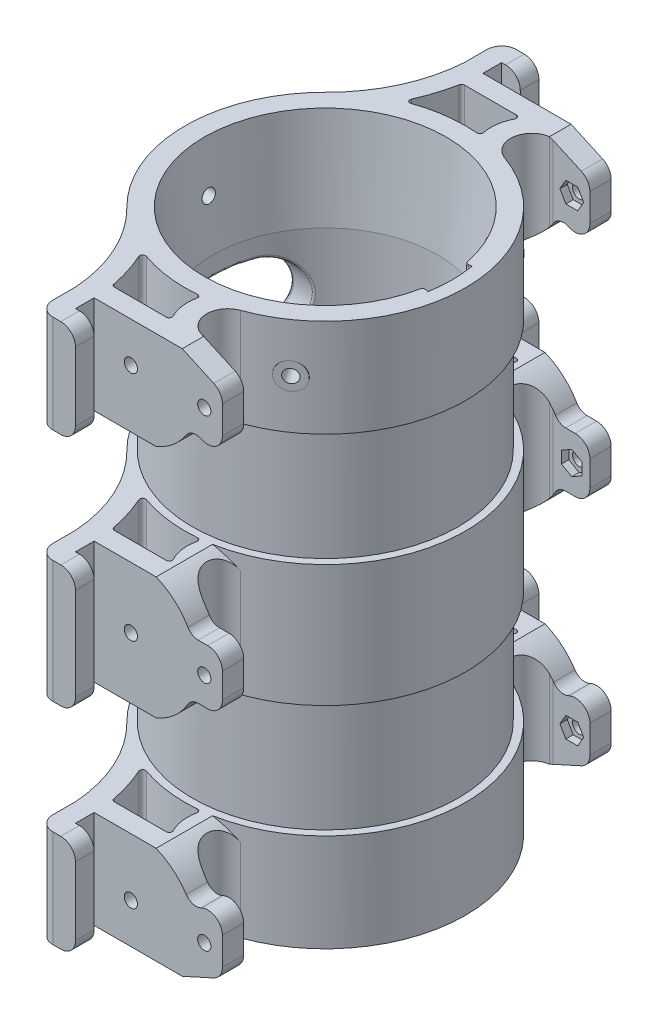
SolidWorks part; units mm, degrees
ref_plane "Front Plane" through (0, 0, 0) normal (0, 0, 1) x (1, 0, 0)
ref_plane "Top Plane" through (0, 0, 0) normal (0, 1, 0) x (1, 0, 0)
ref_plane "Right Plane" through (0, 0, 0) normal (1, 0, 0) x (0, 0, -1)
sketch "Sketch1" plane through (0, 0, 0) normal (0, 1, 0) x (1, 0, 0)
  line L0 (0, 38.25) -> (0, 45.25) construction
  circle A0 centre (0, 0) radius 38.25
  circle A1 centre (0, 0) radius 45.25
  dimension "D1" = 76.5
  dimension "D2" = 7
extrude "Boss-Extrude1" add sketch "Sketch1" along normal mid plane 185
sketch "Sketch2" plane through (0, -92.5, 0) normal (0, -1, 0) x (1, 0, 0)
  line L0 (0, 36.25) -> (0, 38.25) construction
  circle A0 centre (0, 0) radius 36.25
  circle A1 centre (0, 0) radius 38.25 construction
  circle A2 centre (0, 0) radius 38.25
  dimension "D1" = 2
extrude "Boss-Extrude2" add sketch "Sketch2" against normal blind 100 from offset 6.35 offset against normal yes
sketch "Sketch7" plane through (0, 0, 0) normal (1, 0, 0) x (0, 0, -1)
  line L0 (45.25, 92.5) -> (-45.25, 92.5) construction
  line L1 (12.5, 40) -> (-12.5, 40) construction
  line L2 (12.5, 27.5) -> (-12.5, 27.5)
  line L3 (12.5, 52.5) -> (-12.5, 52.5)
  circle A0 centre (0, 40) radius 12.5 construction
  arc A1 (12.5, 27.5) -> (12.5, 52.5) centre (12.5, 40) ccw
  arc A2 (-12.5, 52.5) -> (-12.5, 27.5) centre (-12.5, 40) ccw
  point P7 (0, 40)
  dimension "D2" = 25
  dimension "D3" = 25
  dimension "D1" = 52.5
extrude "Cut-Extrude4" cut sketch "Sketch7" against normal through all
sketch "Sketch8" plane through (0, 0, 0) normal (0, 1, 0) x (1, 0, 0)
  line L1 (17.5, -66.175) -> (128.1882, -66.175) construction
  line L2 (-18.85, -66.175) -> (-18.85, -78.875)
  line L3 (-18.85, -78.875) -> (-6.15, -78.875)
  line L4 (45.25, 0) -> (-45.25, 0) construction
  line L5 (31.75, 0) -> (50, 0) construction
  line L6 (-6.15, -78.875) -> (-6.15, -72.525)
  line L7 (-12.5, -72.525) -> (17.5, -72.525) construction
  line L8 (-6.15, -72.525) -> (-12.5, -72.525)
  line L9 (-12.5, -72.525) -> (-12.5, -66.175)
  line L10 (-12.5, -66.175) -> (43.65, -66.175)
  line L11 (-12.5, 66.175) -> (43.65, 66.175)
  line L12 (-12.5, 72.525) -> (-12.5, 66.175)
  line L13 (-6.15, 72.525) -> (-12.5, 72.525)
  line L14 (-6.15, 78.875) -> (-6.15, 72.525)
  line L15 (-18.85, 78.875) -> (-6.15, 78.875)
  line L16 (-18.85, 66.175) -> (-18.85, 78.875)
  line L18 (43.65, -66.175) -> (43.65, -58.9107)
  line L19 (43.65, -58.9107) -> (18.65, -58.9107)
  line L20 (43.65, 58.9107) -> (18.65, 58.9107)
  line L21 (43.65, 66.175) -> (43.65, 58.9107)
  line L22 (-12.5, -72.525) -> (-18.85, -72.525) construction
  arc A0 (-32.8241, -31.1471) -> (-18.85, -66.175) centre (-69.7381, -66.175) cw
  circle A1 centre (0, 0) radius 45.25 construction
  arc A2 (-32.8241, -31.1471) -> (15.7007, -42.4388) centre (0, 0) ccw
  arc A3 (-32.8241, 31.1471) -> (15.7007, 42.4388) centre (0, 0) cw
  arc A4 (-32.8241, 31.1471) -> (-18.85, 66.175) centre (-69.7381, 66.175) ccw
  arc A9 (18.65, -58.9107) -> (15.7007, -42.4388) centre (18.65, -50.4107) cw
  arc A10 (18.65, 58.9107) -> (15.7007, 42.4388) centre (18.65, 50.4107) ccw
  dimension "D1" = 8.5
  dimension "D2" = 62.5
  dimension "D3" = 25
extrude "Boss-Extrude3" add sketch "Sketch8" along normal up to surface and the other way up to surface up to face at (0, 92.5, 45.25) other way up to face at (0, -92.5, 45.25)
sketch "Sketch10" plane through (0, 0, 66.175) normal (0, 0, 1) x (1, 0, 0)
  line L0 (17.5, -92.5) -> (43.65, -92.5)
  line L1 (43.65, -92.5) -> (43.65, -80.6536)
  line L2 (-6.15, -59.2129) -> (-32.8241, -59.2129)
  line L3 (128.1882, -42.3564) -> (17.5, -92.5) construction
  line L4 (43.65, -80.6536) -> (17.5, -92.5)
  line L5 (43.65, 80.6536) -> (43.65, 92.5)
  line L6 (17.5, 92.5) -> (128.1882, 42.3564) construction
  line L7 (43.65, 92.5) -> (17.5, 92.5)
  line L8 (-12.5, 92.5) -> (43.65, 92.5) construction
  line L9 (17.5, 92.5) -> (43.65, 80.6536)
  line L10 (43.65, -60.1882) -> (43.65, -9.3209)
  line L11 (79.953, -43.7423) -> (23.8431, -69.161) construction
  line L12 (22.9086, -9.3209) -> (60.2886, -9.3209) construction
  line L21 (22.9086, -9.3209) -> (43.65, -9.3209)
  line L23 (43.65, -60.1882) -> (23.8431, -69.161)
  line L25 (-6.15, 92.5) -> (-6.15, -92.5) construction
  line L26 (-32.8241, 92.5) -> (-32.8241, -92.5) construction
  line L32 (-32.8241, -59.2129) -> (-32.8241, -20.7871)
  line L36 (-32.8241, -20.7871) -> (-6.15, -20.7871)
  line L40 (0, 0) -> (-32.8241, 0) construction
  line L45 (8.611, -59.2129) -> (-6.15, -59.2129)
  line L46 (8.611, -20.7871) -> (-6.15, -20.7871)
  line L47 (-32.8241, 59.2129) -> (-32.8241, 20.7871)
  line L48 (-6.15, 59.2129) -> (-32.8241, 59.2129)
  line L49 (8.611, 59.2129) -> (-6.15, 59.2129)
  line L50 (43.65, 60.1882) -> (23.8431, 69.161)
  line L51 (43.65, 60.1882) -> (43.65, 9.3209)
  line L52 (22.9086, 9.3209) -> (43.65, 9.3209)
  line L53 (8.611, 20.7871) -> (-6.15, 20.7871)
  line L54 (-32.8241, 20.7871) -> (-6.15, 20.7871)
  line L55 (43.65, 92.5) -> (43.65, -92.5) construction
  arc A6 (18.8427, -67.7035) -> (23.8431, -69.161) centre (22.1925, -65.5175) ccw construction
  arc A7 (18.8427, -67.7035) -> (8.611, -59.2129) centre (0, -80) ccw construction
  arc A10 (8.611, -20.7871) -> (19.4507, -11.3102) centre (0, 0) ccw construction
  arc A11 (22.9086, -9.3209) -> (19.4507, -11.3102) centre (22.9086, -13.3209) ccw construction
  arc A18 (18.8427, -67.7035) -> (23.8431, -69.161) centre (22.1925, -65.5175) ccw
  arc A19 (18.8427, -67.7035) -> (8.611, -59.2129) centre (0, -80) ccw
  arc A22 (8.611, -20.7871) -> (19.4507, -11.3102) centre (0, 0) ccw
  arc A23 (22.9086, -9.3209) -> (19.4507, -11.3102) centre (22.9086, -13.3209) ccw
  arc A24 (18.8427, 67.7035) -> (8.611, 59.2129) centre (0, 80) cw
  arc A25 (18.8427, 67.7035) -> (23.8431, 69.161) centre (22.1925, 65.5175) cw
  arc A26 (22.9086, 9.3209) -> (19.4507, 11.3102) centre (22.9086, 13.3209) cw
  arc A27 (8.611, 20.7871) -> (19.4507, 11.3102) centre (0, 0) cw
extrude "Cut-Extrude6" cut sketch "Sketch10" against normal up to surface and the other way through all up to face at (-41.5057, 40, 0)
sketch "Sketch11" plane through (0, 0, -78.875) normal (0, 0, -1) x (-1, 0, 0)
  line L3 (-43.65, 92.5) -> (-43.65, 80.6536)
  line L4 (-17.5, 92.5) -> (-43.65, 92.5)
  line L5 (-43.65, 80.6536) -> (-17.5, 92.5)
  line L6 (-43.65, 92.5) -> (-43.65, 80.6536)
  line L7 (-17.5, 92.5) -> (-43.65, 92.5)
  line L8 (-43.65, 80.6536) -> (-17.5, 92.5)
  line L9 (-43.65, -92.5) -> (-17.5, -92.5)
  line L10 (-43.65, -80.6536) -> (-43.65, -92.5)
  line L11 (-17.5, -92.5) -> (-43.65, -80.6536)
  line L12 (-43.65, -92.5) -> (-17.5, -92.5)
  line L13 (-43.65, -80.6536) -> (-43.65, -92.5)
  line L14 (-17.5, -92.5) -> (-43.65, -80.6536)
  line L20 (32.8241, 20.7871) -> (32.8241, 59.2129)
  line L21 (6.15, 20.7871) -> (32.8241, 20.7871)
  line L22 (-8.611, 20.7871) -> (6.15, 20.7871)
  line L23 (-43.65, 9.3209) -> (-22.9086, 9.3209)
  line L24 (-43.65, 60.1882) -> (-43.65, 9.3209)
  line L25 (-23.8431, 69.161) -> (-43.65, 60.1882)
  line L26 (6.15, 59.2129) -> (-8.611, 59.2129)
  line L27 (32.8241, 59.2129) -> (6.15, 59.2129)
  line L28 (32.8241, 20.7871) -> (32.8241, 59.2129)
  line L29 (6.15, 20.7871) -> (32.8241, 20.7871)
  line L30 (-8.611, 20.7871) -> (6.15, 20.7871)
  line L31 (-43.65, 9.3209) -> (-22.9086, 9.3209)
  line L32 (-43.65, 60.1882) -> (-43.65, 9.3209)
  line L33 (-23.8431, 69.161) -> (-43.65, 60.1882)
  line L34 (6.15, 59.2129) -> (-8.611, 59.2129)
  line L35 (32.8241, 59.2129) -> (6.15, 59.2129)
  line L36 (-22.9086, -9.3209) -> (-43.65, -9.3209)
  line L37 (-43.65, -9.3209) -> (-43.65, -60.1882)
  line L38 (-43.65, -60.1882) -> (-23.8431, -69.161)
  line L39 (-8.611, -59.2129) -> (6.15, -59.2129)
  line L40 (6.15, -59.2129) -> (32.8241, -59.2129)
  line L41 (32.8241, -59.2129) -> (32.8241, -20.7871)
  line L42 (32.8241, -20.7871) -> (6.15, -20.7871)
  line L43 (6.15, -20.7871) -> (-8.611, -20.7871)
  line L44 (-22.9086, -9.3209) -> (-43.65, -9.3209)
  line L45 (-43.65, -9.3209) -> (-43.65, -60.1882)
  line L46 (-43.65, -60.1882) -> (-23.8431, -69.161)
  line L47 (-8.611, -59.2129) -> (6.15, -59.2129)
  line L48 (6.15, -59.2129) -> (32.8241, -59.2129)
  line L49 (32.8241, -59.2129) -> (32.8241, -20.7871)
  line L50 (32.8241, -20.7871) -> (6.15, -20.7871)
  line L51 (6.15, -20.7871) -> (-8.611, -20.7871)
  arc A4 (-8.611, 20.7871) -> (-19.4507, 11.3102) centre (0, 0) ccw
  arc A5 (-22.9086, 9.3209) -> (-19.4507, 11.3102) centre (-22.9086, 13.3209) ccw
  arc A6 (-18.8427, 67.7035) -> (-23.8431, 69.161) centre (-22.1925, 65.5175) ccw
  arc A7 (-18.8427, 67.7035) -> (-8.611, 59.2129) centre (0, 80) ccw
  arc A8 (-8.611, 20.7871) -> (-19.4507, 11.3102) centre (0, 0) ccw
  arc A9 (-22.9086, 9.3209) -> (-19.4507, 11.3102) centre (-22.9086, 13.3209) ccw
  arc A10 (-18.8427, 67.7035) -> (-23.8431, 69.161) centre (-22.1925, 65.5175) ccw
  arc A11 (-18.8427, 67.7035) -> (-8.611, 59.2129) centre (0, 80) ccw
  arc A12 (-23.8431, -69.161) -> (-18.8427, -67.7035) centre (-22.1925, -65.5175) ccw
  arc A13 (-8.611, -59.2129) -> (-18.8427, -67.7035) centre (0, -80) ccw
  arc A14 (-19.4507, -11.3102) -> (-8.611, -20.7871) centre (0, 0) ccw
  arc A15 (-19.4507, -11.3102) -> (-22.9086, -9.3209) centre (-22.9086, -13.3209) ccw
  arc A16 (-23.8431, -69.161) -> (-18.8427, -67.7035) centre (-22.1925, -65.5175) ccw
  arc A17 (-8.611, -59.2129) -> (-18.8427, -67.7035) centre (0, -80) ccw
  arc A18 (-19.4507, -11.3102) -> (-8.611, -20.7871) centre (0, 0) ccw
  arc A19 (-19.4507, -11.3102) -> (-22.9086, -9.3209) centre (-22.9086, -13.3209) ccw
  dimension "D1" = 0
  dimension "D2" = 0
  dimension "D3" = 0
  dimension "D4" = 0
extrude "Cut-Extrude7" cut sketch "Sketch11" against normal up to surface (66.9486 mm away) up to face at (-3.9052, 0.3336, 17.6166)
fillet "Fillet5" radius 5 6 edges at (-18.85, -75.8565, -78.875) (-18.85, 0, -78.875) (-18.85, 75.8565, -78.875) (-18.85, 0, 78.875) (-18.85, -75.8565, 78.875) (-18.85, 75.8565, 78.875)
sketch "Sketch14" plane through (0, 0, -66.175) normal (0, 0, -1) x (-1, 0, 0)
  line L0 (0, 0) -> (-25, 0) construction
  line L5 (-25, 78.8696) -> (-25, 0) construction
  circle A3 centre (-25, 78.8696) radius 2.25
  circle A5 centre (-25, 0) radius 2.25
  circle A7 centre (-25, -78.8696) radius 2.25
  circle A8 centre (0, 0) radius 2.25
  circle A9 centre (0, 78.8696) radius 2.25
  circle A10 centre (0, -78.8696) radius 2.25
  dimension "D1" = 25
  dimension "D2" = 78.8696
  dimension "D3" = 4.5
extrude "Cut-Extrude8" cut sketch "Sketch14" against normal up to surface (7.2643 mm away) up to face at (27.8361, -73.0039, -58.9107)
sketch "Sketch15" plane through (0, 0, 66.175) normal (0, 0, 1) x (1, 0, 0)
  circle A1 centre (0, -78.8696) radius 2.25
  circle A3 centre (0, -78.8696) radius 2.25
  circle A5 centre (0, 78.8696) radius 2.25
  circle A7 centre (0, 78.8696) radius 2.25
  circle A9 centre (0, 0) radius 2.25
  circle A11 centre (0, 0) radius 2.25
  circle A13 centre (25, 78.8696) radius 2.25
  circle A14 centre (25, 78.8696) radius 2.25
  circle A15 centre (25, -78.8696) radius 2.25
  circle A16 centre (25, -78.8696) radius 2.25
  circle A17 centre (25, 0) radius 2.25
  circle A18 centre (25, 0) radius 2.25
  dimension "D1" = 0
  dimension "D2" = 0
  dimension "D3" = 0
  dimension "D4" = 0
  dimension "D5" = 0
  dimension "D6" = 0
extrude "Cut-Extrude9" cut sketch "Sketch15" against normal up to surface (7.2643 mm away) up to face at (27.8361, -73.0039, 58.9107)
sketch "Sketch16" plane through (0, 92.5, 0) normal (0, 1, 0) x (1, 0, 0)
  line L0 (-45.25, 0) -> (-47.75, 0) construction
  circle A0 centre (0, 0) radius 47.75
  circle A1 centre (0, 0) radius 45.25
  arc A2 (-32.8241, 31.1471) -> (-32.8241, -31.1471) centre (0, 0) ccw construction
  dimension "D1" = 2.5
extrude "Boss-Extrude4" add sketch "Sketch16" against normal up to surface (33.2871 mm away) up to face at (-10.3824, 59.2129, 65.577)
sketch "Sketch17" plane through (0, -92.5, 0) normal (0, -1, 0) x (1, 0, 0)
  circle A1 centre (0, 0) radius 45.25
  circle A2 centre (0, 0) radius 45.25
  circle A3 centre (0, 0) radius 47.75
  circle A4 centre (0, 0) radius 47.75
  dimension "D1" = 0
  dimension "D2" = 0
extrude "Boss-Extrude5" add sketch "Sketch17" against normal up to surface (33.2871 mm away) up to face at (-10.3824, -59.2129, 65.577)
sketch "Sketch18" plane through (0, -20.7871, 0) normal (0, -1, 0) x (1, 0, 0)
  circle A1 centre (0, 0) radius 47.75
  circle A2 centre (0, 0) radius 47.75
  circle A3 centre (0, 0) radius 45.25
  circle A4 centre (0, 0) radius 45.25
  dimension "D1" = 0
  dimension "D2" = 0
extrude "Boss-Extrude6" add sketch "Sketch18" against normal up to surface (41.5741 mm away) up to face at (-10.3824, 20.7871, 65.577)
sketch "Sketch20" plane through (0, 0, 0) normal (1, 0, 0) x (0, 0, -1)
  line L0 (-45.25, -20.7871) -> (45.25, -20.7871) construction
  line L1 (46.9672, -59.2129) -> (-46.9672, -59.2129) construction
  line L2 (-45.25, 59.2129) -> (45.25, 59.2129) construction
  line L3 (46.9672, 20.7871) -> (-46.9672, 20.7871) construction
  line L4 (-45.25, -20.7871) -> (45.25, -20.7871) construction
  line L5 (46.9672, -59.2129) -> (-46.9672, -59.2129) construction
  line L6 (-45.25, 59.2129) -> (45.25, 59.2129) construction
  line L7 (46.9672, 20.7871) -> (-46.9672, 20.7871) construction
  line L8 (0, -20.7871) -> (0, -59.2129) construction
  line L9 (0, 59.2129) -> (0, 20.7871) construction
  line L10 (-10, 40) -> (10, 40) construction
  line L11 (-10, 45) -> (10, 45)
  line L12 (-10, 35) -> (10, 35)
  line L13 (0, 0) -> (46.4328, 0) construction
  line L14 (46.4328, 19.5496) -> (46.4328, -19.5496) construction
  line L15 (-10, -40) -> (10, -40) construction
  line L16 (-10, -45) -> (10, -45)
  line L17 (-10, -35) -> (10, -35)
  arc A2 (-10, 45) -> (-10, 35) centre (-10, 40) ccw
  arc A3 (10, 35) -> (10, 45) centre (10, 40) ccw
  arc A4 (-10, -45) -> (-10, -35) centre (-10, -40) cw
  arc A5 (10, -35) -> (10, -45) centre (10, -40) cw
  point P2 (0, 40)
  point P14 (0, -20.7871)
  point P30 (0, -40)
  dimension "D1" = 20
  dimension "D2" = 5
extrude "Cut-Extrude10" [suppressed] cut sketch "Sketch20" along normal through all
pattern_circular "CirPattern1" [suppressed] count 6 over 360 reverse direction yes of bodies 118
ref_plane "Plane1" through (-26.1107, -92.5, 39.9787) normal (0, -1, 0) x (-1, 0, 0)
sketch "Sketch23" plane through (0, -92.5, 0) normal (0, -1, 0) x (1, 0, 0)
  line L0 (0, 0) -> (-47.75, 0) construction
  arc A0 (-18.85, 66.175) -> (-33.5786, 33.9491) centre (-68.7395, 69.4978) cw
  arc A1 (-26.1107, 39.9787) -> (-26.1107, -39.9787) centre (0, 0) ccw construction
  arc A2 (-33.5786, 33.9491) -> (-26.1107, 39.9787) centre (0, 0) cw
  arc A3 (-18.85, 66.175) -> (-26.1107, 39.9787) centre (-69.7381, 66.175) cw
  arc A4 (-18.85, -66.175) -> (-26.1107, -39.9787) centre (-69.7381, -66.175) ccw
  arc A5 (-33.5786, -33.9491) -> (-26.1107, -39.9787) centre (0, 0) ccw
  arc A6 (-18.85, -66.175) -> (-33.5786, -33.9491) centre (-68.7395, -69.4978) ccw
  arc A7 (-26.1107, 39.9787) -> (-18.85, 66.175) centre (-69.7381, 66.175) ccw construction
  dimension "D1" = 50
extrude "Boss-Extrude7" add sketch "Sketch23" against normal up to surface (33.2871 mm away) up to face at (-8.8243, -59.2129, 0)
sketch "Sketch24" plane through (0, 92.5, 0) normal (0, 1, 0) x (1, 0, 0)
  arc A3 (-26.1107, 39.9787) -> (-18.85, 66.175) centre (-69.7381, 66.175) ccw
  arc A4 (-26.1107, 39.9787) -> (-33.5786, 33.9491) centre (0, 0) ccw
  arc A5 (-33.5786, 33.9491) -> (-18.85, 66.175) centre (-68.7395, 69.4978) ccw
  arc A6 (-26.1107, 39.9787) -> (-18.85, 66.175) centre (-69.7381, 66.175) ccw
  arc A7 (-26.1107, 39.9787) -> (-33.5786, 33.9491) centre (0, 0) ccw
  arc A8 (-33.5786, 33.9491) -> (-18.85, 66.175) centre (-68.7395, 69.4978) ccw
  arc A9 (-18.85, -66.175) -> (-33.5786, -33.9491) centre (-68.7395, -69.4978) ccw
  arc A10 (-33.5786, -33.9491) -> (-26.1107, -39.9787) centre (0, 0) ccw
  arc A11 (-18.85, -66.175) -> (-26.1107, -39.9787) centre (-69.7381, -66.175) ccw
  arc A12 (-18.85, -66.175) -> (-33.5786, -33.9491) centre (-68.7395, -69.4978) ccw
  arc A13 (-33.5786, -33.9491) -> (-26.1107, -39.9787) centre (0, 0) ccw
  arc A14 (-18.85, -66.175) -> (-26.1107, -39.9787) centre (-69.7381, -66.175) ccw
  dimension "D1" = 0
  dimension "D2" = 0
extrude "Boss-Extrude8" add sketch "Sketch24" against normal up to surface (33.2871 mm away) up to face at (-45.25, 59.2129, 0)
sketch "Sketch25" plane through (0, 20.7871, 0) normal (0, 1, 0) x (1, 0, 0)
  arc A3 (-18.85, -66.175) -> (-33.5786, -33.9491) centre (-68.7395, -69.4978) ccw
  arc A4 (-33.5786, -33.9491) -> (-26.1107, -39.9787) centre (0, 0) ccw
  arc A5 (-18.85, -66.175) -> (-26.1107, -39.9787) centre (-69.7381, -66.175) ccw
  arc A6 (-18.85, -66.175) -> (-33.5786, -33.9491) centre (-68.7395, -69.4978) ccw
  arc A7 (-33.5786, -33.9491) -> (-26.1107, -39.9787) centre (0, 0) ccw
  arc A8 (-18.85, -66.175) -> (-26.1107, -39.9787) centre (-69.7381, -66.175) ccw
  arc A9 (-26.1107, 39.9787) -> (-18.85, 66.175) centre (-69.7381, 66.175) ccw
  arc A10 (-33.5786, 33.9491) -> (-18.85, 66.175) centre (-68.7395, 69.4978) ccw
  arc A11 (-26.1107, 39.9787) -> (-33.5786, 33.9491) centre (0, 0) ccw
  arc A12 (-26.1107, 39.9787) -> (-18.85, 66.175) centre (-69.7381, 66.175) ccw
  arc A13 (-33.5786, 33.9491) -> (-18.85, 66.175) centre (-68.7395, 69.4978) ccw
  arc A14 (-26.1107, 39.9787) -> (-33.5786, 33.9491) centre (0, 0) ccw
  dimension "D1" = 0
  dimension "D2" = 0
extrude "Boss-Extrude9" add sketch "Sketch25" against normal up to surface (41.5741 mm away) up to face at (-45.25, -20.7871, 0)
sketch "Sketch27" plane through (0, 0, 0) normal (0, 0, 1) x (1, 0, 0)
  line L0 (38.25, 59.2129) -> (41.1622, 92.5)
  line L3 (38.25, 59.2129) -> (0, 59.2129) construction
  line L5 (-18.85, 92.5) -> (-33.5786, 92.5) construction
  line L6 (38.25, 59.2129) -> (38.25, 92.5)
  line L7 (38.25, 92.5) -> (41.1622, 92.5)
  line L8 (0, 59.2129) -> (0, 92.5) construction
  dimension "D1" = 33.2871
  dimension "D2" = 5
  dimension "D3" = 38.25
  dimension "D4" = 38.25
  dimension "D5" = 38.25
revolve "Cut-Revolve1" cut sketch "Sketch27" angle 360 about L8
sketch "Sketch28" plane through (0, 92.5, 0) normal (0, 1, 0) x (1, 0, 0)
  line L1 (43.65, 58.9107) -> (18.65, 58.9107) construction
  line L2 (0, 0) -> (47.75, 0) construction
  line L3 (11.1383, 46.4328) -> (10.15, 46.6698)
  line L4 (10.15, 46.6698) -> (10.15, 58.8326)
  line L5 (10.15, 58.8326) -> (17.5, 58.8326)
  line L6 (10.15, -58.8326) -> (17.5, -58.8326)
  line L7 (10.15, -46.6698) -> (10.15, -58.8326)
  line L8 (11.1383, -46.4328) -> (10.15, -46.6698)
  arc A0 (17.5, 58.8326) -> (16.1276, 44.944) centre (18.5576, 51.716) ccw
  arc A1 (11.1383, -46.4328) -> (11.1383, 46.4328) centre (0, 0) ccw construction
  arc A2 (16.1276, 44.944) -> (11.1383, 46.4328) centre (0, 0) ccw
  arc A7 (17.5, 58.8326) -> (11.1383, 46.4328) centre (18.65, 50.4107) ccw construction
  arc A8 (16.1276, -44.944) -> (11.1383, -46.4328) centre (0, 0) cw
  arc A9 (17.5, -58.8326) -> (16.1276, -44.944) centre (18.5576, -51.716) cw
extrude "Boss-Extrude13" add sketch "Sketch28" against normal up to surface (26.6421 mm away) up to face at (13.4579, 62.8457, 57.713)
sketch "Sketch29" plane through (0, -92.5, 0) normal (0, -1, 0) x (1, 0, 0)
  line L3 (11.1383, -46.4328) -> (10.15, -46.6698)
  line L4 (10.15, -46.6698) -> (10.15, -58.8326)
  line L5 (10.15, -58.8326) -> (17.5, -58.8326)
  line L6 (11.1383, -46.4328) -> (10.15, -46.6698)
  line L7 (10.15, -46.6698) -> (10.15, -58.8326)
  line L8 (10.15, -58.8326) -> (17.5, -58.8326)
  line L9 (17.5, 58.8326) -> (10.15, 58.8326)
  line L10 (10.15, 46.6698) -> (11.1383, 46.4328)
  line L11 (10.15, 58.8326) -> (10.15, 46.6698)
  line L12 (17.5, 58.8326) -> (10.15, 58.8326)
  line L13 (10.15, 46.6698) -> (11.1383, 46.4328)
  line L14 (10.15, 58.8326) -> (10.15, 46.6698)
  arc A2 (16.1276, -44.944) -> (17.5, -58.8326) centre (18.5576, -51.716) ccw
  arc A3 (11.1383, -46.4328) -> (16.1276, -44.944) centre (0, 0) ccw
  arc A4 (16.1276, -44.944) -> (17.5, -58.8326) centre (18.5576, -51.716) ccw
  arc A5 (11.1383, -46.4328) -> (16.1276, -44.944) centre (0, 0) ccw
  arc A6 (17.5, 58.8326) -> (16.1276, 44.944) centre (18.5576, 51.716) ccw
  arc A7 (16.1276, 44.944) -> (11.1383, 46.4328) centre (0, 0) ccw
  arc A8 (17.5, 58.8326) -> (16.1276, 44.944) centre (18.5576, 51.716) ccw
  arc A9 (16.1276, 44.944) -> (11.1383, 46.4328) centre (0, 0) ccw
  dimension "D1" = 0
  dimension "D2" = 0
extrude "Boss-Extrude14" add sketch "Sketch29" against normal up to surface (32.0496 mm away) up to face at (13.7418, -62.9735, 57.3608)
sketch "Sketch30" plane through (0, 0, 0) normal (0, 1, 0) x (1, 0, 0)
  line L3 (10.15, 46.6698) -> (11.1383, 46.4328)
  line L4 (10.15, 58.8326) -> (10.15, 46.6698)
  line L5 (17.5, 58.8326) -> (10.15, 58.8326)
  line L6 (10.15, 46.6698) -> (11.1383, 46.4328)
  line L7 (10.15, 58.8326) -> (10.15, 46.6698)
  line L8 (17.5, 58.8326) -> (10.15, 58.8326)
  line L9 (10.15, -46.6698) -> (10.15, -58.8326)
  line L10 (10.15, -58.8326) -> (17.5, -58.8326)
  line L11 (11.1383, -46.4328) -> (10.15, -46.6698)
  line L12 (10.15, -46.6698) -> (10.15, -58.8326)
  line L13 (10.15, -58.8326) -> (17.5, -58.8326)
  line L14 (11.1383, -46.4328) -> (10.15, -46.6698)
  arc A2 (17.5, 58.8326) -> (16.1276, 44.944) centre (18.5576, 51.716) ccw
  arc A3 (16.1276, 44.944) -> (11.1383, 46.4328) centre (0, 0) ccw
  arc A4 (17.5, 58.8326) -> (16.1276, 44.944) centre (18.5576, 51.716) ccw
  arc A5 (16.1276, 44.944) -> (11.1383, 46.4328) centre (0, 0) ccw
  arc A6 (16.1276, -44.944) -> (17.5, -58.8326) centre (18.5576, -51.716) ccw
  arc A7 (11.1383, -46.4328) -> (16.1276, -44.944) centre (0, 0) ccw
  arc A8 (16.1276, -44.944) -> (17.5, -58.8326) centre (18.5576, -51.716) ccw
  arc A9 (11.1383, -46.4328) -> (16.1276, -44.944) centre (0, 0) ccw
  dimension "D1" = 0
  dimension "D2" = 0
extrude "Boss-Extrude15" add sketch "Sketch30" against normal up to surface and the other way up to surface up to face at (13.9691, -16.7184, -57.3608) other way up to face at (13.6851, 16.8462, -57.713)
ref_plane "Plane2" through (0, 75.8565, 0) normal (0, 1, 0) x (1, 0, 0)
sketch "Sketch31" plane through (0, 75.8565, 0) normal (0, 1, 0) x (1, 0, 0)
  line L0 (0, 0) -> (27.3883, 39.1145) construction
  line L1 (0, 0) -> (-47.75, 0) construction
  arc A0 (16.1276, -44.944) -> (16.1276, 44.944) centre (0, 0) ccw construction
  arc A1 (-33.5786, 33.9491) -> (-33.5786, -33.9491) centre (0, 0) ccw construction
  dimension "D1" = 125
ref_plane "Plane3" through (27.3883, 75.8565, -39.1145) normal (0.5736, 0, -0.8192) x (-0.8192, 0, -0.5736)
sketch "Sketch34" [suppressed] plane through (0, 75.8565, 0) normal (0, 1, 0) x (1, 0, 0)
  line L1 (-18.85, 66.175) -> (-18.85, 73.875)
  line L2 (0, 0) -> (-47.75, 0) construction
  line L4 (-18.85, -66.175) -> (-18.85, -73.875)
  arc A0 (-13.85, 78.875) -> (-18.85, 73.875) centre (-13.85, 73.875) ccw construction
  arc A2 (-46.2179, 11.9988) -> (-33.5786, 33.9491) centre (0, 0) cw
  arc A3 (-33.5786, 33.9491) -> (-18.85, 66.175) centre (-68.7395, 69.4978) ccw
  arc A4 (-18.85, 73.875) -> (-18.0639, 76.5663) centre (-13.85, 73.875) cw
  arc A10 (-33.5786, 33.9491) -> (-33.5786, -33.9491) centre (0, 0) ccw construction
  arc A11 (-46.2179, 11.9988) -> (-18.0639, 76.5663) centre (171.5626, -44.5402) cw
  arc A12 (-33.5786, 33.9491) -> (-18.85, 66.175) centre (-68.7395, 69.4978) ccw construction
  arc A13 (-46.2179, -11.9988) -> (-18.0639, -76.5663) centre (171.5626, 44.5402) ccw
  arc A14 (-18.85, -73.875) -> (-18.0639, -76.5663) centre (-13.85, -73.875) ccw
  arc A15 (-33.5786, -33.9491) -> (-18.85, -66.175) centre (-68.7395, -69.4978) cw
  arc A16 (-46.2179, -11.9988) -> (-33.5786, -33.9491) centre (0, 0) ccw
  dimension "D1" = 225
extrude "Boss-Extrude17" [suppressed] add sketch "Sketch34" along normal mid plane 10
ref_plane "Plane4" [suppressed] through (0, 0, 0) normal (0, -1, 0) x (-1, 0, 0)
ref_plane "Plane5" [suppressed] through (0, -75.8565, 0) normal (0, -1, 0) x (-1, 0, 0)
sketch "Sketch35" [suppressed] plane through (0, 0, 0) normal (0, -1, 0) x (-1, 0, 0)
  line L1 (18.85, 73.875) -> (18.85, 66.175)
  line L2 (18.85, 73.875) -> (18.85, 66.175)
  line L3 (18.85, -66.175) -> (18.85, -73.875)
  line L4 (18.85, -66.175) -> (18.85, -73.875)
  arc A4 (46.2179, 11.9988) -> (18.0639, 76.5663) centre (-171.5626, -44.5402) ccw
  arc A5 (18.85, 73.875) -> (18.0639, 76.5663) centre (13.85, 73.875) ccw
  arc A6 (18.85, 66.175) -> (33.5786, 33.9491) centre (68.7395, 69.4978) ccw
  arc A7 (46.2179, 11.9988) -> (33.5786, 33.9491) centre (0, 0) ccw
  arc A8 (46.2179, 11.9988) -> (18.0639, 76.5663) centre (-171.5626, -44.5402) ccw
  arc A9 (18.85, 73.875) -> (18.0639, 76.5663) centre (13.85, 73.875) ccw
  arc A10 (18.85, 66.175) -> (33.5786, 33.9491) centre (68.7395, 69.4978) ccw
  arc A11 (46.2179, 11.9988) -> (33.5786, 33.9491) centre (0, 0) ccw
  arc A12 (18.0639, -76.5663) -> (18.85, -73.875) centre (13.85, -73.875) ccw
  arc A13 (18.0639, -76.5663) -> (46.2179, -11.9988) centre (-171.5626, 44.5402) ccw
  arc A14 (33.5786, -33.9491) -> (46.2179, -11.9988) centre (0, 0) ccw
  arc A15 (33.5786, -33.9491) -> (18.85, -66.175) centre (68.7395, -69.4978) ccw
  arc A16 (18.0639, -76.5663) -> (18.85, -73.875) centre (13.85, -73.875) ccw
  arc A17 (18.0639, -76.5663) -> (46.2179, -11.9988) centre (-171.5626, 44.5402) ccw
  arc A18 (33.5786, -33.9491) -> (46.2179, -11.9988) centre (0, 0) ccw
  arc A19 (33.5786, -33.9491) -> (18.85, -66.175) centre (68.7395, -69.4978) ccw
  dimension "D1" = 0
  dimension "D2" = 0
extrude "Boss-Extrude18" [suppressed] add sketch "Sketch35" along normal mid plane 10
sketch "Sketch36" [suppressed] plane through (0, -75.8565, 0) normal (0, -1, 0) x (-1, 0, 0)
  line L1 (18.85, 73.875) -> (18.85, 66.175)
  line L2 (18.85, 73.875) -> (18.85, 66.175)
  line L3 (18.85, -66.175) -> (18.85, -73.875)
  line L4 (18.85, -66.175) -> (18.85, -73.875)
  arc A4 (46.2179, 11.9988) -> (18.0639, 76.5663) centre (-171.5626, -44.5402) ccw
  arc A5 (18.85, 73.875) -> (18.0639, 76.5663) centre (13.85, 73.875) ccw
  arc A6 (18.85, 66.175) -> (33.5786, 33.9491) centre (68.7395, 69.4978) ccw
  arc A7 (46.2179, 11.9988) -> (33.5786, 33.9491) centre (0, 0) ccw
  arc A8 (46.2179, 11.9988) -> (18.0639, 76.5663) centre (-171.5626, -44.5402) ccw
  arc A9 (18.85, 73.875) -> (18.0639, 76.5663) centre (13.85, 73.875) ccw
  arc A10 (18.85, 66.175) -> (33.5786, 33.9491) centre (68.7395, 69.4978) ccw
  arc A11 (46.2179, 11.9988) -> (33.5786, 33.9491) centre (0, 0) ccw
  arc A12 (18.0639, -76.5663) -> (18.85, -73.875) centre (13.85, -73.875) ccw
  arc A13 (18.0639, -76.5663) -> (46.2179, -11.9988) centre (-171.5626, 44.5402) ccw
  arc A14 (33.5786, -33.9491) -> (46.2179, -11.9988) centre (0, 0) ccw
  arc A15 (33.5786, -33.9491) -> (18.85, -66.175) centre (68.7395, -69.4978) ccw
  arc A16 (18.0639, -76.5663) -> (18.85, -73.875) centre (13.85, -73.875) ccw
  arc A17 (18.0639, -76.5663) -> (46.2179, -11.9988) centre (-171.5626, 44.5402) ccw
  arc A18 (33.5786, -33.9491) -> (46.2179, -11.9988) centre (0, 0) ccw
  arc A19 (33.5786, -33.9491) -> (18.85, -66.175) centre (68.7395, -69.4978) ccw
  dimension "D1" = 0
  dimension "D2" = 0
extrude "Boss-Extrude19" [suppressed] add sketch "Sketch36" along normal mid plane 10
sketch "Sketch32" plane through (27.3883, 75.8565, -39.1145) normal (0.5736, 0, -0.8192) x (-0.8192, 0, -0.5736)
  circle A0 centre (0, 0) radius 4.5
  dimension "D1" = 9
extrude "Boss-Extrude16" add sketch "Sketch32" against normal blind 1
sketch "Sketch33" plane through (27.3883, 0, -39.1145) normal (0.5736, 0, -0.8192) x (-0.8192, 0, -0.5736)
  circle A0 centre (0, 75.8565) radius 2.25
  dimension "D1" = 4.5
extrude "Cut-Extrude11" cut sketch "Sketch33" against normal up to surface (8.1077 mm away) up to face at (0, 92.5, -41.1622)
pattern_circular "CirPattern2" count 3 over 250 about axis through (0, -75.8444, 0) along (0, 1, 0) of "Boss-Extrude16", "Cut-Extrude11"
sketch "Sketch37" plane through (0, 0, 58.9107) normal (0, 0, -1) x (-1, 0, 0)
  line L1 (-2.0207, -3.5) -> (2.0207, -3.5)
  line L2 (2.0207, -3.5) -> (4.0415, 0)
  line L3 (4.0415, 0) -> (2.0207, 3.5)
  line L4 (2.0207, 3.5) -> (-2.0207, 3.5)
  line L5 (-2.0207, 3.5) -> (-4.0415, 0)
  line L6 (-4.0415, 0) -> (-2.0207, -3.5)
  line L13 (-28.5, 2.0207) -> (-28.5, -2.0207)
  line L14 (-28.5, -2.0207) -> (-25, -4.0415)
  line L15 (-25, -4.0415) -> (-21.5, -2.0207)
  line L16 (-21.5, -2.0207) -> (-21.5, 2.0207)
  line L17 (-21.5, 2.0207) -> (-25, 4.0415)
  line L18 (-25, 4.0415) -> (-28.5, 2.0207)
  line L25 (-29.0415, -78.8696) -> (-27.0207, -82.3696)
  line L26 (-27.0207, -82.3696) -> (-22.9793, -82.3696)
  line L27 (-22.9793, -82.3696) -> (-20.9585, -78.8696)
  line L28 (-20.9585, -78.8696) -> (-22.9793, -75.3696)
  line L29 (-22.9793, -75.3696) -> (-27.0207, -75.3696)
  line L30 (-27.0207, -75.3696) -> (-29.0415, -78.8696)
  line L37 (-2.0207, -82.3696) -> (2.0207, -82.3696)
  line L38 (2.0207, -82.3696) -> (4.0415, -78.8696)
  line L39 (4.0415, -78.8696) -> (2.0207, -75.3696)
  line L40 (2.0207, -75.3696) -> (-2.0207, -75.3696)
  line L41 (-2.0207, -75.3696) -> (-4.0415, -78.8696)
  line L42 (-4.0415, -78.8696) -> (-2.0207, -82.3696)
  line L43 (-2.0207, 75.3696) -> (2.0207, 75.3696)
  line L44 (2.0207, 75.3696) -> (4.0415, 78.8696)
  line L45 (4.0415, 78.8696) -> (2.0207, 82.3696)
  line L46 (2.0207, 82.3696) -> (-2.0207, 82.3696)
  line L47 (-2.0207, 82.3696) -> (-4.0415, 78.8696)
  line L48 (-4.0415, 78.8696) -> (-2.0207, 75.3696)
  line L49 (-27.0207, 75.3696) -> (-22.9793, 75.3696)
  line L50 (-22.9793, 75.3696) -> (-20.9585, 78.8696)
  line L51 (-20.9585, 78.8696) -> (-22.9793, 82.3696)
  line L52 (-22.9793, 82.3696) -> (-27.0207, 82.3696)
  line L53 (-27.0207, 82.3696) -> (-29.0415, 78.8696)
  line L54 (-29.0415, 78.8696) -> (-27.0207, 75.3696)
  circle A1 centre (-25, -78.8696) radius 2.25 construction
  circle A3 centre (-25, 0) radius 2.25 construction
  circle A5 centre (0, 0) radius 2.25 construction
  circle A7 centre (-25, -78.8696) radius 2.25 construction
  circle A9 centre (-25, 0) radius 2.25 construction
  circle A11 centre (0, 0) radius 2.25 construction
  circle A12 centre (0, 0) radius 3.5 construction
  circle A13 centre (0, 78.8696) radius 2.25 construction
  circle A14 centre (-25, 0) radius 3.5 construction
  circle A15 centre (-25, 78.8696) radius 2.25 construction
  circle A16 centre (-25, -78.8696) radius 3.5 construction
  circle A17 centre (0, -78.8696) radius 2.25 construction
  circle A18 centre (0, 78.8696) radius 2.25 construction
  circle A19 centre (-25, 78.8696) radius 2.25 construction
  circle A20 centre (0, -78.8696) radius 2.25 construction
  circle A21 centre (0, -78.8696) radius 3.5 construction
  circle A22 centre (0, 78.8696) radius 3.5 construction
  circle A23 centre (-25, 78.8696) radius 3.5 construction
  dimension "D2" = 7
  dimension "D3" = 4.0415
extrude "Cut-Extrude12" cut sketch "Sketch37" against normal blind 2.5
sketch "Sketch39" plane through (0, 0, -58.9107) normal (0, 0, 1) x (1, 0, 0)
  line L78 (-2.0207, -82.3696) -> (2.0207, -82.3696)
  line L79 (-4.0415, -78.8696) -> (-2.0207, -82.3696)
  line L80 (-2.0207, -75.3696) -> (-4.0415, -78.8696)
  line L81 (2.0207, -75.3696) -> (-2.0207, -75.3696)
  line L82 (4.0415, -78.8696) -> (2.0207, -75.3696)
  line L83 (2.0207, -82.3696) -> (4.0415, -78.8696)
  line L84 (-2.0207, -82.3696) -> (2.0207, -82.3696)
  line L85 (-4.0415, -78.8696) -> (-2.0207, -82.3696)
  line L86 (-2.0207, -75.3696) -> (-4.0415, -78.8696)
  line L87 (2.0207, -75.3696) -> (-2.0207, -75.3696)
  line L88 (4.0415, -78.8696) -> (2.0207, -75.3696)
  line L89 (2.0207, -82.3696) -> (4.0415, -78.8696)
  line L90 (-2.0207, -3.5) -> (2.0207, -3.5)
  line L91 (-4.0415, 0) -> (-2.0207, -3.5)
  line L92 (-2.0207, 3.5) -> (-4.0415, 0)
  line L93 (2.0207, 3.5) -> (-2.0207, 3.5)
  line L94 (4.0415, 0) -> (2.0207, 3.5)
  line L95 (2.0207, -3.5) -> (4.0415, 0)
  line L96 (-2.0207, -3.5) -> (2.0207, -3.5)
  line L97 (-4.0415, 0) -> (-2.0207, -3.5)
  line L98 (-2.0207, 3.5) -> (-4.0415, 0)
  line L99 (2.0207, 3.5) -> (-2.0207, 3.5)
  line L100 (4.0415, 0) -> (2.0207, 3.5)
  line L101 (2.0207, -3.5) -> (4.0415, 0)
  line L102 (-2.0207, 75.3696) -> (2.0207, 75.3696)
  line L103 (-4.0415, 78.8696) -> (-2.0207, 75.3696)
  line L104 (-2.0207, 82.3696) -> (-4.0415, 78.8696)
  line L105 (2.0207, 82.3696) -> (-2.0207, 82.3696)
  line L106 (4.0415, 78.8696) -> (2.0207, 82.3696)
  line L107 (2.0207, 75.3696) -> (4.0415, 78.8696)
  line L108 (-2.0207, 75.3696) -> (2.0207, 75.3696)
  line L109 (-4.0415, 78.8696) -> (-2.0207, 75.3696)
  line L110 (-2.0207, 82.3696) -> (-4.0415, 78.8696)
  line L111 (2.0207, 82.3696) -> (-2.0207, 82.3696)
  line L112 (4.0415, 78.8696) -> (2.0207, 82.3696)
  line L113 (2.0207, 75.3696) -> (4.0415, 78.8696)
  line L114 (28.5, -2.0207) -> (28.5, 2.0207)
  line L115 (25, -4.0415) -> (28.5, -2.0207)
  line L116 (21.5, -2.0207) -> (25, -4.0415)
  line L117 (21.5, 2.0207) -> (21.5, -2.0207)
  line L118 (25, 4.0415) -> (21.5, 2.0207)
  line L119 (28.5, 2.0207) -> (25, 4.0415)
  line L120 (28.5, -2.0207) -> (28.5, 2.0207)
  line L121 (25, -4.0415) -> (28.5, -2.0207)
  line L122 (21.5, -2.0207) -> (25, -4.0415)
  line L123 (21.5, 2.0207) -> (21.5, -2.0207)
  line L124 (25, 4.0415) -> (21.5, 2.0207)
  line L125 (28.5, 2.0207) -> (25, 4.0415)
  line L126 (22.9793, 75.3696) -> (27.0207, 75.3696)
  line L127 (20.9585, 78.8696) -> (22.9793, 75.3696)
  line L128 (22.9793, 82.3696) -> (20.9585, 78.8696)
  line L129 (27.0207, 82.3696) -> (22.9793, 82.3696)
  line L130 (29.0415, 78.8696) -> (27.0207, 82.3696)
  line L131 (27.0207, 75.3696) -> (29.0415, 78.8696)
  line L132 (22.9793, 75.3696) -> (27.0207, 75.3696)
  line L133 (20.9585, 78.8696) -> (22.9793, 75.3696)
  line L134 (22.9793, 82.3696) -> (20.9585, 78.8696)
  line L135 (27.0207, 82.3696) -> (22.9793, 82.3696)
  line L136 (29.0415, 78.8696) -> (27.0207, 82.3696)
  line L137 (27.0207, 75.3696) -> (29.0415, 78.8696)
  line L138 (22.9793, -82.3696) -> (27.0207, -82.3696)
  line L139 (20.9585, -78.8696) -> (22.9793, -82.3696)
  line L140 (22.9793, -75.3696) -> (20.9585, -78.8696)
  line L141 (27.0207, -75.3696) -> (22.9793, -75.3696)
  line L142 (29.0415, -78.8696) -> (27.0207, -75.3696)
  line L143 (27.0207, -82.3696) -> (29.0415, -78.8696)
  line L144 (22.9793, -82.3696) -> (27.0207, -82.3696)
  line L145 (20.9585, -78.8696) -> (22.9793, -82.3696)
  line L146 (22.9793, -75.3696) -> (20.9585, -78.8696)
  line L147 (27.0207, -75.3696) -> (22.9793, -75.3696)
  line L148 (29.0415, -78.8696) -> (27.0207, -75.3696)
  line L149 (27.0207, -82.3696) -> (29.0415, -78.8696)
  dimension "D1" = 0
  dimension "D2" = 0
  dimension "D3" = 0
  dimension "D4" = 0
  dimension "D5" = 0
  dimension "D6" = 0
extrude "Cut-Extrude13" cut sketch "Sketch39" against normal blind 2.5
sketch "Sketch44" plane through (0, 0, 0) normal (0, 0, 1) x (1, 0, 0)
  line L0 (41.1622, 92.5) -> (-41.1622, 92.5) construction
  line L1 (41.1622, 92.5) -> (-41.1622, 92.5) construction
  line L2 (41.1622, 92.5) -> (43.1622, 92.5)
  line L3 (38.25, 59.2129) -> (-38.25, 59.2129) construction
  line L4 (38.25, 59.2129) -> (-38.25, 59.2129) construction
  line L5 (38.25, 59.2129) -> (40.25, 59.2129)
  line L6 (40.25, 59.2129) -> (43.1622, 92.5)
  line L7 (38.25, 59.2129) -> (41.1622, 92.5)
  line L8 (0, 59.2129) -> (0, 92.5) construction
  dimension "D1" = 2
revolve "Cut-Revolve2" cut sketch "Sketch44" angle 10 about L8 other way angle 10
fillet "Fillet6" radius 1 2 edges at (39.1029, 75.8565, -6.8949) (39.1029, 75.8565, 6.8949)
sketch "Sketch45" plane through (0, 92.5, 0) normal (0, 1, 0) x (1, 0, 0)
  line L3 (0, 0) -> (47.75, 0) construction
  line L4 (-12.5, 59.5872) -> (7.2438, 59.5872)
  line L5 (-13.0263, 59.5872) -> (7.2438, 59.5872)
  line L6 (-13.0263, -59.5872) -> (7.2438, -59.5872)
  circle A0 centre (0, 0) radius 47.75 construction
  arc A1 (16.1276, -44.944) -> (16.1276, 44.944) centre (0, 0) ccw construction
  arc A2 (5.456, 47.4373) -> (-18.1353, 44.1721) centre (0, 0) ccw
  arc A3 (-18.1353, -44.1721) -> (-13.0263, -59.5872) centre (-68.7395, -69.4978) cw
  arc A4 (5.456, -47.4373) -> (-18.1353, -44.1721) centre (0, 0) cw
  arc A5 (7.2438, -59.5872) -> (5.456, -47.4373) centre (18.5576, -51.716) cw
  arc A6 (-28.946, 29.2653) -> (-12.2768, 65.7372) centre (-68.7395, 69.4978) ccw
  arc A7 (-18.1353, 44.1721) -> (-13.0263, 59.5872) centre (-68.7395, 69.4978) ccw
  arc A9 (7.2438, 59.5872) -> (13.9025, 38.7434) centre (18.5576, 51.716) ccw
  arc A10 (7.2438, 59.5872) -> (5.456, 47.4373) centre (18.5576, 51.716) ccw
  dimension "D1" = 6.5878
  dimension "D2" = 6.5878
extrude "Cut-Extrude14" cut sketch "Sketch45" against normal through all both and the other way through all
fillet "Fillet7" radius 1 24 edges at (5.456, 75.8565, 47.4373) (5.456, 0, 47.4373) (5.456, -75.8565, 47.4373) (7.2438, 75.8565, 59.5872) (-13.0263, 75.8565, 59.5872) (-18.1353, 75.8565, 44.1721) (-18.1353, 0, 44.1721) (-18.1353, -75.8565, 44.1721) (-18.1353, 75.8565, -44.1721) (-18.1353, 0, -44.1721) (-18.1353, -75.8565, -44.1721) (5.456, 0, -47.4373) (5.456, -75.8565, -47.4373) (7.2438, 75.8565, -59.5872) (-13.0263, 75.8565, -59.5872) (5.456, 75.8565, -47.4373)
sketch "Sketch47" plane through (0, 0, 66.175) normal (0, 0, 1) x (1, 0, 0)
  line L0 (31.15, 9.3209) -> (31.15, -9.3209) construction
  line L1 (43.65, 9.3209) -> (22.9086, 9.3209) construction
  line L2 (22.9086, -9.3209) -> (43.65, -9.3209) construction
  line L3 (43.65, 9.3209) -> (43.65, -9.3209) construction
  line L4 (17.5, -92.5) -> (43.65, -80.6536) construction
  line L5 (31.15, -86.3163) -> (43.65, -86.3163)
  line L6 (31.15, -86.3163) -> (31.15, 86.3163)
  line L7 (31.15, 86.3163) -> (43.65, 86.3163)
  line L8 (43.65, -86.3163) -> (43.65, 86.3163)
  line L10 (43.65, 80.6536) -> (17.5, 92.5) construction
  dimension "D1" = 12.5
extrude "Shorten_(editable)" cut sketch "Sketch47" against normal up to surface (7.2643 mm away) up to face at (25, 78.8696, 58.9107)
sketch "Sketch48" plane through (0, 0, -66.175) normal (0, 0, -1) x (-1, 0, 0)
  line L4 (-43.65, -86.3163) -> (-31.15, -86.3163)
  line L5 (-43.65, 86.3163) -> (-43.65, -86.3163)
  line L6 (-31.15, 86.3163) -> (-43.65, 86.3163)
  line L7 (-31.15, -86.3163) -> (-31.15, 86.3163)
  line L8 (-43.65, -86.3163) -> (-31.15, -86.3163)
  line L9 (-43.65, 86.3163) -> (-43.65, -86.3163)
  line L10 (-31.15, 86.3163) -> (-43.65, 86.3163)
  line L11 (-31.15, -86.3163) -> (-31.15, 86.3163)
  dimension "D1" = 0
extrude "Cut-Extrude16" cut sketch "Sketch48" against normal up to surface (7.2643 mm away) up to face at (25, 78.8696, -58.9107)
fillet "Fillet8" radius 5 24 edges at (31.15, 86.3163, -62.5429) (31.15, 65.8509, -62.5429) (31.15, 9.3209, -62.5429) (31.15, -9.3209, -62.5429) (31.15, -65.8509, -62.5429) (31.15, -86.3163, -62.5429) (31.15, -86.3163, 62.5429) (31.15, -65.8509, 62.5429) (31.15, -9.3209, 62.5429) (31.15, 9.3209, 62.5429) (31.15, 86.3163, 62.5429) (31.15, 65.8509, 62.5429) (-6.15, -59.2129, -75.7) (-6.15, -92.5, -75.7) (-6.15, -20.7871, -75.7) (-6.15, 20.7871, -75.7) (-6.15, 59.2129, -75.7) (-6.15, 92.5, -75.7) (-6.15, 92.5, 75.7) (-6.15, 59.2129, 75.7) (-6.15, -20.7871, 75.7) (-6.15, 20.7871, 75.7) (-6.15, -59.2129, 75.7) (-6.15, -92.5, 75.7)
fillet "Fillet9" radius 1 8 edges at (-45.25, 52.5, 0) (-37.7613, 41.2941, -24.9328) (-45.25, 27.5, 0) (-38.25, 52.5, 0) (-28.9895, 41.0782, -24.9534) (-38.25, 27.5, 0) (-37.7613, 38.7059, 24.9328) (-28.9895, 38.9218, 24.9534)
